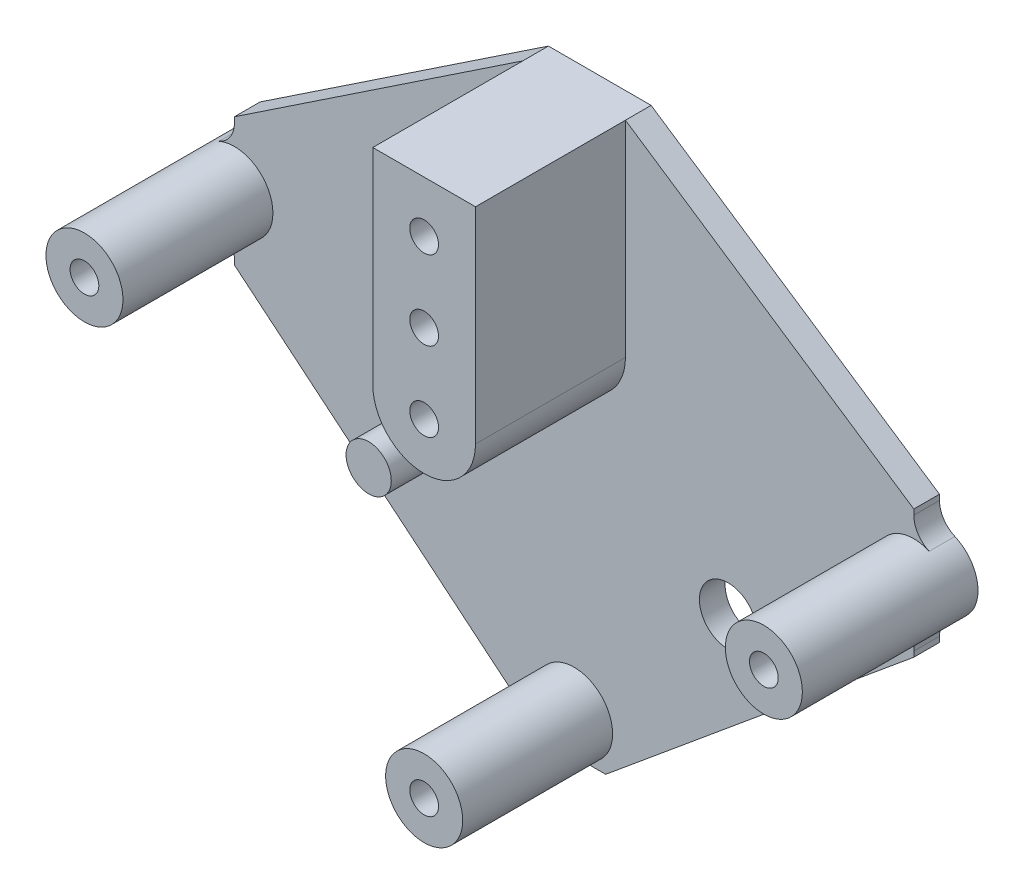
SolidWorks part; units mm, degrees
ref_plane "Front" through (0, 0, 0) normal (0, 0, 1) x (1, 0, 0)
ref_plane "Top" through (0, 0, 0) normal (0, 1, 0) x (1, 0, 0)
ref_plane "Right" through (0, 0, 0) normal (1, 0, 0) x (0, 0, -1)
sketch "Sketch1" plane through (0, 0, 0) normal (0, 0, 1) x (1, 0, 0)
  line L1 (0, 0) -> (84.008, 0)
  line L2 (0, 0) -> (0, 71.2724)
  line L3 (0, 71.2724) -> (84.008, 71.2724)
  line L4 (84.008, 0) -> (84.008, 71.2724)
  dimension "D1" = 84.008
  dimension "D2" = 71.2724
extrude "Boss-Extrude1" add sketch "Sketch1" along normal blind 3.175
sketch "Sketch5" plane through (0, 0, 3.175) normal (0, 0, 1) x (1, 0, 0)
  line L0 (84.008, 0) -> (84.008, 71.2724) construction
  line L1 (0, 71.2724) -> (0, 0) construction
  line L2 (0, 0) -> (84.008, 0) construction
  circle A0 centre (84.008, 39.525) radius 4.7625
  circle A1 centre (0, 39.525) radius 4.7625
  dimension "D1" = 39.525
  dimension "D3" = 9.525
  dimension "D4" = 9.525
  dimension "D2" = 39.525
extrude "Boss-Extrude3" add sketch "Sketch5" against normal up to surface (3.175 mm away) up to face at (42.004, 35.6362, 0)
sketch "Sketch3" plane through (0, 0, 3.175) normal (0, 0, 1) x (1, 0, 0)
  line L0 (0, 0) -> (84.008, 0) construction
  circle A0 centre (42.004, 4.7625) radius 1.8415
  point P4 (42.004, 0)
  dimension "D1" = 3.683
  dimension "D2" = 4.7625
extrude "Cut-Extrude1" cut sketch "Sketch3" against normal through all
sketch "Sketch6" plane through (0, 0, 3.175) normal (0, 0, 1) x (1, 0, 0)
  line L1 (35.654, 71.2724) -> (48.354, 71.2724)
  line L2 (35.654, 71.2724) -> (35.654, 45.8724)
  line L4 (48.354, 71.2724) -> (48.354, 45.8724)
  line L5 (84.008, 71.2724) -> (0, 71.2724) construction
  circle A0 centre (84.008, 39.525) radius 4.7625
  circle A1 centre (0, 39.525) radius 4.7625
  circle A2 centre (42.004, 4.7625) radius 4.7625
  arc A3 (48.354, 45.8724) -> (35.654, 45.8724) centre (42.004, 45.8724) cw
  point P10 (42.004, 39.5224)
  point P13 (42.004, 71.2724)
  point P16 (42.004, 71.2724)
  dimension "D1" = 9.525
  dimension "D2" = 9.525
  dimension "D3" = 9.525
  dimension "D6" = 6.35
  dimension "D4" = 12.7
  dimension "D5" = 31.75
extrude "Boss-Extrude4" add sketch "Sketch6" along normal blind 18.542
sketch "Sketch4" plane through (0, 0, 3.175) normal (0, 0, 1) x (1, 0, 0)
  line L1 (84.008, 71.2724) -> (48.354, 71.2724) construction
  line L2 (84.008, 71.2724) -> (0, 71.2724) construction
  circle A0 centre (42.004, 64.9224) radius 1.778
  circle A1 centre (42.004, 55.1434) radius 1.778
  circle A2 centre (42.004, 45.3644) radius 1.778
  point P8 (42.004, 71.2724)
  dimension "D1" = 3.556
  dimension "D2" = 6.35
  dimension "D3" = 19.558
  dimension "D4" = 9.779
extrude "Cut-Extrude2" cut sketch "Sketch4" along normal through all both and the other way through all
sketch "Sketch7" plane through (0, 0, 0) normal (0, 0, -1) x (-1, 0, 0)
  circle A0 centre (-42.004, 4.7625) radius 1.778
  circle A1 centre (0, 39.525) radius 1.778
  circle A2 centre (-84.008, 39.525) radius 1.778
  dimension "D1" = 3.556
extrude "Cut-Extrude3" cut sketch "Sketch7" against normal through all
sketch "Sketch8" plane through (0, 0, 0) normal (0, 0, -1) x (-1, 0, 0)
  circle A0 centre (-61.054, 24.525) radius 3.556
  circle A1 centre (-22.954, 24.525) radius 1.905
  circle A2 centre (-42.004, 4.7625) radius 1.8415 construction
  dimension "D1" = 38.1
  dimension "D2" = 7.112
  dimension "D3" = 3.81
  dimension "D5" = 19.7625
  dimension "D6" = 19.7625
  dimension "D4" = 19.05
extrude "Cut-Extrude4" cut sketch "Sketch8" against normal through all
sketch "Sketch9" plane through (0, 0, 0) normal (0, 0, -1) x (-1, 0, 0)
  line L0 (-84.008, 0) -> (-84.008, 31.5875)
  line L1 (-84.008, 0) -> (-84.008, 34.7625) construction
  line L2 (-84.008, 31.5875) -> (-45.908, 0)
  line L3 (0, 0) -> (-84.008, 0) construction
  line L4 (-45.908, 0) -> (-84.008, 0)
  line L5 (-84.008, 71.2724) -> (-84.008, 47.4625)
  line L6 (-84.008, 44.2875) -> (-84.008, 71.2724) construction
  line L7 (-84.008, 47.4625) -> (-48.354, 71.2724)
  line L8 (-48.354, 71.2724) -> (-84.008, 71.2724)
  dimension "D1" = 38.1
  dimension "D2" = 3.175
  dimension "D3" = 3.175
extrude "Cut-Extrude5" cut sketch "Sketch9" against normal through all
ref_plane "Plane1" through (42.004, 0, 0) normal (1, 0, 0) x (0, 0, -1)
mirror "Mirror1" about plane through (42.004, 0, 0) normal (1, 0, 0) of "Cut-Extrude5"
fillet "Fillet1" radius 3.175 4 edges at (0, 34.7625, 1.5875) (0, 44.2875, 1.5875) (84.008, 44.2875, 1.5875) (84.008, 34.7625, 1.5875)
sketch "Sketch10" plane through (0, 0, 3.175) normal (0, 0, 1) x (1, 0, 0)
  circle A0 centre (22.954, 24.525) radius 2.794
  dimension "D1" = 5.588
extrude "Boss-Extrude5" add sketch "Sketch10" along normal blind 6.35
sketch "Sketch11" plane through (0, 0, 3.175) normal (0, 0, -1) x (-1, 0, 0)
  circle A0 centre (-22.954, 24.525) radius 1.905
  dimension "D1" = 3.81
extrude "Boss-Extrude6" add sketch "Sketch11" along normal up to surface (3.175 mm away) up to face at (57.498, 24.525, 0)
